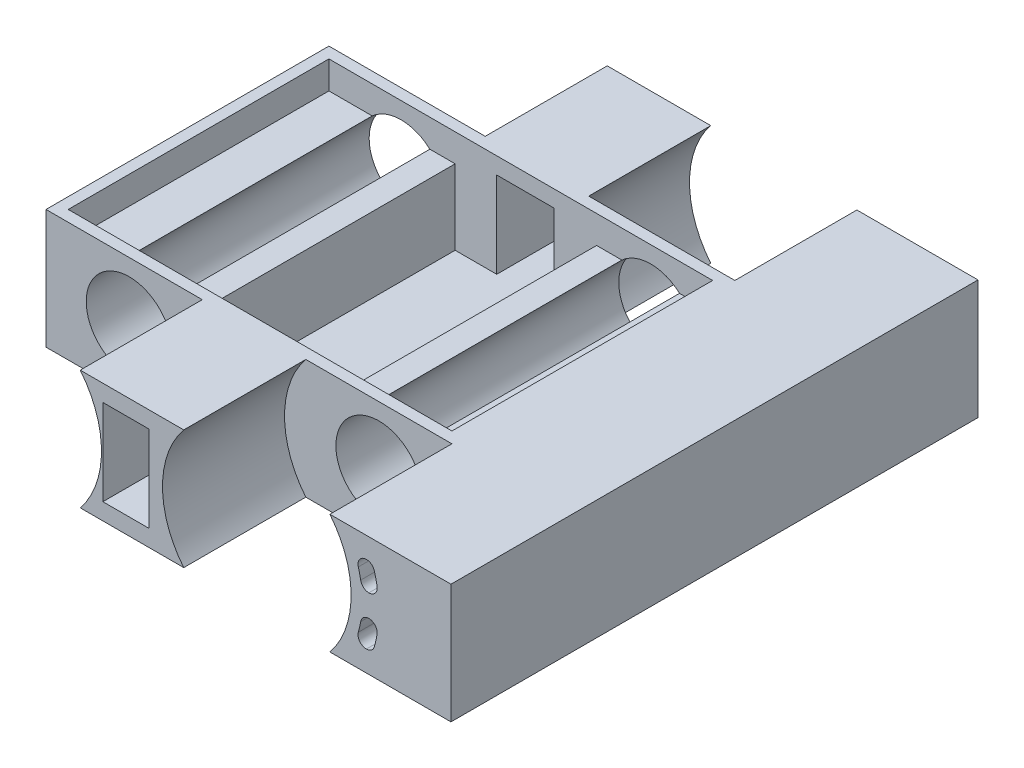
SolidWorks part; units mm, degrees
ref_plane "Front Plane" through (0, 0, 0) normal (0, 0, 1) x (1, 0, 0)
ref_plane "Top Plane" through (0, 0, 0) normal (0, 1, 0) x (1, 0, 0)
ref_plane "Right Plane" through (0, 0, 0) normal (1, 0, 0) x (0, 0, -1)
sketch "Sketch1" plane through (0, 0, 0) normal (0, 1, 0) x (1, 0, 0)
  line L1 (-44.2281, 29.9937) -> (50.7719, 29.9937)
  line L2 (-44.2281, 29.9937) -> (-44.2281, -65.0063)
  line L3 (-44.2281, -65.0063) -> (50.7719, -65.0063)
  line L4 (50.7719, 29.9937) -> (50.7719, -65.0063)
  dimension "D1" = 95
  dimension "D2" = 95
extrude "Boss-Extrude1" add sketch "Sketch1" along normal blind 25
sketch "Sketch2" plane through (0, 0, 65.0063) normal (0, 0, 1) x (1, 0, 0)
  line L1 (-44.2281, 0) -> (50.7719, 0) construction
  line L2 (-44.2281, 25) -> (-44.2281, 0) construction
  circle A0 centre (-29.2281, 10.75) radius 7.75
  circle A1 centre (15.7719, 10.75) radius 7.75
  point P6 (-44.2281, 12.5)
  dimension "D1" = 45
  dimension "D2" = 10.75
  dimension "D3" = 15
extrude "Cut-Extrude2" cut sketch "Sketch2" against normal blind 100
sketch "Sketch3" plane through (0, 0, 65.0063) normal (0, 0, 1) x (1, 0, 0)
  line L0 (-44.2281, 0) -> (50.7719, 0) construction
  circle A0 centre (-29.2281, 10.75) radius 17
  circle A1 centre (15.7719, 10.75) radius 17
  point P7 (-28.0903, 8.1892)
  dimension "D1" = 45
  dimension "D2" = 10.75
extrude "Cut-Extrude3" cut sketch "Sketch3" against normal blind 22
sketch "Sketch4" plane through (0, 0, -29.9937) normal (0, 0, -1) x (-1, 0, 0)
  circle A0 centre (-15.7719, 10.75) radius 17
  circle A1 centre (29.2281, 10.75) radius 17
extrude "Cut-Extrude4" cut sketch "Sketch4" against normal blind 22
sketch "Sketch5" plane through (0, 0, 65.0063) normal (0, 0, 1) x (1, 0, 0)
  line L1 (-44.2281, 25) -> (-37.9811, 25)
  line L2 (-44.2281, 25) -> (-44.2281, 0)
  line L3 (-44.2281, 0) -> (-37.9811, 0)
  line L4 (-37.9811, 25) -> (-37.9811, 0)
extrude "Cut-Extrude5" cut sketch "Sketch5" against normal blind 22
sketch "Sketch6" plane through (0, 0, -29.9937) normal (0, 0, -1) x (-1, 0, 0)
  line L1 (44.2281, 25) -> (37.0493, 25)
  line L2 (44.2281, 25) -> (44.2281, 0)
  line L3 (44.2281, 0) -> (37.0493, 0)
  line L4 (37.0493, 25) -> (37.0493, 0)
extrude "Cut-Extrude6" cut sketch "Sketch6" against normal blind 22
sketch "Sketch8" plane through (0, 0, -29.9937) normal (0, 0, -1) x (-1, 0, 0)
  line L1 (-50.7719, 25) -> (48.732, 25)
  line L2 (-50.7719, 25) -> (-50.7719, 21.5)
  line L3 (-50.7719, 21.5) -> (48.732, 21.5)
  line L4 (48.732, 25) -> (48.732, 21.5)
  dimension "D1" = 3.5
extrude "Cut-Extrude7" cut sketch "Sketch8" against normal blind 100
sketch "Sketch9" plane through (0, 0, 65.0063) normal (0, 0, 1) x (1, 0, 0)
  line L0 (-16.0585, 0) -> (2.6024, 0) construction
  line L1 (-11.9781, 18.5) -> (-3.6781, 18.5)
  line L2 (-11.9781, 18.5) -> (-11.9781, 3)
  line L3 (-11.9781, 3) -> (-3.6781, 3)
  line L4 (-3.6781, 18.5) -> (-3.6781, 3)
  arc A0 (-16.0585, 0) -> (-16.0585, 21.5) centre (-29.2281, 10.75) ccw construction
  circle A1 centre (15.7719, 10.75) radius 7.75 construction
  dimension "D1" = 8.3
  dimension "D2" = 15.5
  dimension "D3" = 3
  dimension "D4" = 17.25
  dimension "D5" = 19.45
extrude "Cut-Extrude11" cut sketch "Sketch9" against normal blind 100
sketch "Sketch13" plane through (-3.6781, 0, 0) normal (-1, 0, 0) x (0, 0, 1)
  line L0 (-29.9937, 3) -> (65.0063, 3) construction
  line L1 (-25.9937, 3) -> (61.0063, 3)
  line L2 (-25.9937, 3) -> (-25.9937, 18.5)
  line L3 (-25.9937, 18.5) -> (61.0063, 18.5)
  line L4 (61.0063, 3) -> (61.0063, 18.5)
  line L5 (-29.9937, 18.5) -> (65.0063, 18.5) construction
  line L6 (-29.9937, 3) -> (-29.9937, 18.5) construction
  line L7 (65.0063, 3) -> (65.0063, 18.5) construction
  dimension "D1" = 4
  dimension "D2" = 4
extrude "Cut-Extrude12" cut sketch "Sketch13" against normal blind 2
sketch "Sketch14" plane through (0, 21.5, 0) normal (0, 1, 0) x (1, 0, 0)
  line L2 (6.0219, 5.9937) -> (6.0219, -41.0063)
  line L4 (-19.4781, 5.9937) -> (-19.4781, -41.0063)
  line L7 (6.0219, 5.9937) -> (-19.4781, 5.9937)
  line L9 (6.0219, -41.0063) -> (-19.4781, -41.0063)
  dimension "D2" = 2
extrude "Cut-Extrude14" cut sketch "Sketch14" against normal blind 18.5
sketch "Sketch16" plane through (0, 21.5, 0) normal (0, 1, 0) x (1, 0, 0)
  line L0 (-44.2281, -43.0063) -> (-44.2281, 7.9937) construction
  line L1 (-17.4781, 5.9937) -> (-42.2281, 5.9937)
  line L2 (-17.4781, 5.9937) -> (-17.4781, -41.0063)
  line L3 (-17.4781, -41.0063) -> (-42.2281, -41.0063)
  line L4 (-42.2281, 5.9937) -> (-42.2281, -41.0063)
  line L5 (-44.2281, -43.0063) -> (-16.0585, -43.0063) construction
  line L6 (-16.0585, 7.9937) -> (-44.2281, 7.9937) construction
  dimension "D1" = 2
  dimension "D2" = 2
  dimension "D3" = 2
  dimension "D4" = 2
extrude "Cut-Extrude15" cut sketch "Sketch16" against normal blind 5
sketch "Sketch17" plane through (0, 21.5, 0) normal (0, 1, 0) x (1, 0, 0)
  line L0 (2.6024, -43.0063) -> (28.9415, -43.0063) construction
  line L1 (6.0219, 5.9937) -> (26.9415, 5.9937)
  line L2 (6.0219, 5.9937) -> (6.0219, -41.0063)
  line L3 (6.0219, -41.0063) -> (26.9415, -41.0063)
  line L4 (26.9415, 5.9937) -> (26.9415, -41.0063)
  dimension "D1" = 2
  dimension "D2" = 2
extrude "Cut-Extrude16" cut sketch "Sketch17" against normal blind 5
sketch "Sketch18" plane through (0, 0, 65.0063) normal (0, 0, 1) x (1, 0, 0)
  line L0 (34.6664, 12.75) -> (37.6809, 12.75)
  line L2 (34.6664, 8.75) -> (37.6809, 8.75)
  line L3 (33.4355, 17.75) -> (36.6286, 17.75)
  line L4 (33.4355, 3.75) -> (36.6286, 3.75)
  arc A0 (36.6286, 3.75) -> (37.6809, 8.75) centre (15.7719, 10.75) ccw
  arc A1 (33.4355, 3.75) -> (34.6664, 8.75) centre (15.7719, 10.75) ccw
  arc A2 (34.6664, 12.75) -> (33.4355, 17.75) centre (15.7719, 10.75) ccw
  arc A3 (37.6809, 12.75) -> (36.6286, 17.75) centre (15.7719, 10.75) ccw
  dimension "D1" = 44
  dimension "D2" = 38
  dimension "D4" = 5
  dimension "D6" = 5
extrude "Cut-Extrude17" cut sketch "Sketch18" against normal blind 100
fillet "Fillet6" radius 1.5 2 edges at (33.4355, 17.75, 17.5063) (36.6286, 17.75, 17.5063)
fillet "Fillet7" radius 1.5 2 edges at (37.6809, 12.75, 17.5063) (34.6664, 12.75, 17.5063)
fillet "Fillet8" radius 1.5 2 edges at (33.4355, 3.75, 17.5063) (36.6286, 3.75, 17.5063)
fillet "Fillet9" radius 1.5 2 edges at (37.6809, 8.75, 17.5063) (34.6664, 8.75, 17.5063)
sketch "Sketch19" plane through (0, 0, 65.0063) normal (0, 0, 1) x (1, 0, 0)
  line L0 (28.9415, 0) -> (50.7719, 0) construction
  line L1 (32.8112, 0) -> (-56.0103, 0)
  line L2 (32.8112, 0) -> (32.8112, 32.5099)
  line L3 (32.8112, 32.5099) -> (-56.0103, 32.5099)
  line L4 (-56.0103, 0) -> (-56.0103, 32.5099)
